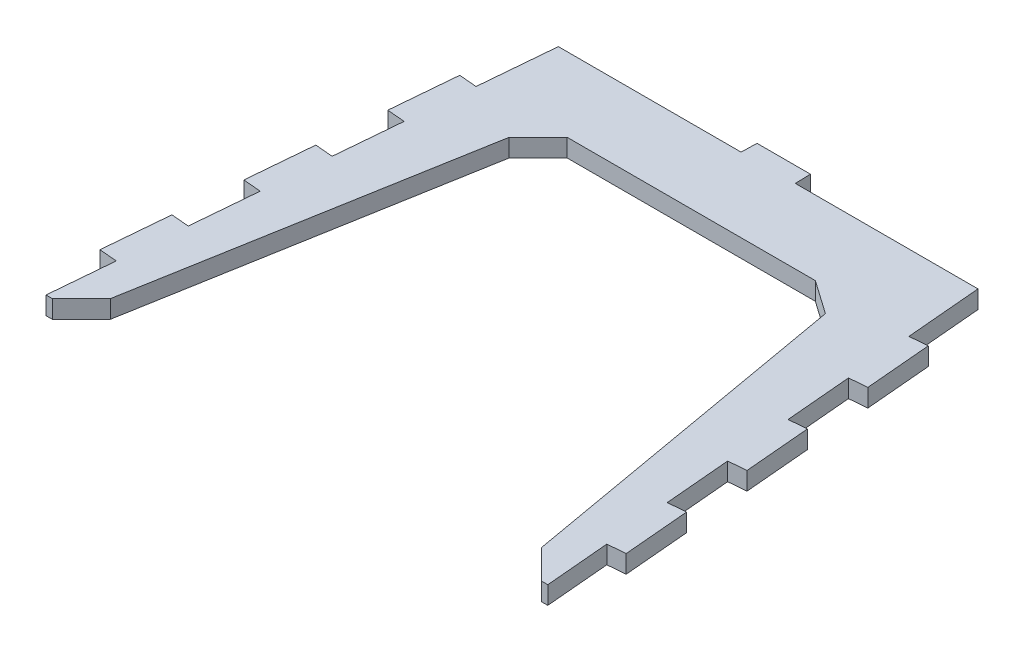
SolidWorks part; units mm, degrees
note: '?' marks a value the reader was unsure of.
ref_plane "Front Plane" through (0, 0, 0) normal (0, 0, 1) x (1, 0, 0)
ref_plane "Top Plane" through (0, 0, 0) normal (0, 1, 0) x (1, 0, 0)
ref_plane "Right Plane" through (0, 0, 0) normal (1, 0, 0) x (0, 0, -1)
ref_axis "Axis1" through (-88.99, 0, 0) along (1, 0, 0)?
ref_axis "Axis2" through (88.99, 0, -993.4582) along (0.0868, 0, 0.9962)?
ref_axis "Axis3" through (-170.7796, 0, -55) along (0.0868, 0, -0.9962)?
ref_point "Point1"
ref_point "Point2"
ref_axis "Axis6" through (-196.0379, 0, 62.0462) along (1, 0, 0)?
sketch "Sketch2" plane through (0, 0, 0) normal (0, 1, 0) x (1, 0, 0)
  line L0 (-190.6304, 0) -> (-225, -394.3588)
  line L1 (190.6304, 0) -> (225, -394.3588)
  line L2 (225, -394.3588) -> (-225, -394.3588) construction
  line L3 (225, -394.3588) -> (220.173, -338.9734) construction
  line L4 (-225, -394.3588) -> (-220.173, -338.9734) construction
  line L5 (-190.6304, 0) -> (190.6304, 0)
  line L6 (-88.99, 0) -> (88.99, 0) construction
  line L7 (0, 0) -> (0, -394.3588) construction
  line L8 (-175.5731, 0) -> (-209.9427, -394.3588) construction
  line L9 (175.5731, 0) -> (209.9427, -394.3588) construction
  line L10 (88.99, 993.4582) -> (170.7796, 55) construction
  line L11 (-170.7796, 55) -> (88.99, 3035.609) construction
  line L12 (-225, -394.3588) -> (-184.6553, -394.3588)
  line L13 (-184.6553, -394.3588) -> (-126.1737, -62.0462)
  line L14 (-126.1737, -62.0462) -> (126.1737, -62.0462)
  line L15 (126.1737, -62.0462) -> (184.6553, -394.3588)
  line L16 (184.6553, -394.3588) -> (225, -394.3588)
  line L18 (-204.9433, -394.3588) -> (-153.1585, 0) construction
  line L19 (-204.9433, -394.3588) -> (-224.7731, -391.7549) construction
  line L20 (-196.0379, -62.0462) -> (196.0379, -62.0462) construction
  dimension "D1" = 5
  dimension "D2" = 20
extrude "Boss-Extrude1" add sketch "Sketch2" against normal up to vertex (15 mm away)
chamfer "Chamfer1" distance 20 angle 45 2 edges at (-184.6553, -7.5, 394.3588) (184.6553, -7.5, 394.3588)
chamfer "Chamfer2" distance 20 angle 45 2 edges at (126.1737, -7.5, 62.0462) (-126.1737, -7.5, 62.0462)
sketch "Sketch3" plane through (0, 0, 0) normal (0, 1, 0) x (1, 0, 0)
  line L0 (196.0379, -62.0462) -> (-196.0379, -62.0462) construction
  line L1 (-126.1737, -62.0462) -> (126.1737, -62.0462) construction
  line L2 (-190.6304, 0) -> (-225, -394.3588) construction
  line L3 (-225, -394.3588) -> (225, -394.3588) construction
  line L4 (225, -394.3588) -> (190.6304, 0) construction
  line L5 (190.6304, 0) -> (-190.6304, 0) construction
  line L6 (-190.6304, 0) -> (190.6304, 0) construction
  line L7 (-190.6304, 0) -> (-225, -394.3588) construction
  line L8 (190.6304, 0) -> (225, -394.3588) construction
  line L9 (225, -394.3588) -> (-225, -394.3588) construction
  line L10 (-175.5731, 0) -> (-209.9427, -394.3588) construction
  line L11 (175.5731, 0) -> (209.9427, -394.3588) construction
  line L12 (175.5731, 0) -> (209.9427, -394.3588) construction
  line L13 (-175.5731, 0) -> (-209.9427, -394.3588) construction
  line L14 (-196.0379, -62.0462) -> (-181.0941, -63.3486)
  line L15 (-181.0941, -63.3486) -> (-175.5731, 0)
  line L16 (-175.5731, 0) -> (-190.6304, 0)
  line L17 (-190.6304, 0) -> (-196.0379, -62.0462)
  line L18 (-210.5189, -228.2025) -> (-195.5752, -229.5049)
  line L19 (-195.5752, -229.5049) -> (-200.4022, -284.8903)
  line L20 (-200.4022, -284.8903) -> (-215.346, -283.5879)
  line L21 (-215.346, -283.5879) -> (-210.5189, -228.2025)
  line L22 (-220.173, -338.9734) -> (-225, -394.3588)
  line L23 (-225, -394.3588) -> (-209.9427, -394.3588)
  line L24 (-209.9427, -394.3588) -> (-205.2292, -340.2758)
  line L25 (-205.2292, -340.2758) -> (-220.173, -338.9734)
  line L26 (-200.8649, -117.4317) -> (-205.6919, -172.8171)
  line L27 (-205.6919, -172.8171) -> (-190.7481, -174.1195)
  line L28 (-190.7481, -174.1195) -> (-185.9211, -118.7341)
  line L29 (-185.9211, -118.7341) -> (-200.8649, -117.4317)
  line L30 (-188.566, -62.6974) -> (-193.393, -118.0829) construction
  line L31 (-198.22, -173.4683) -> (-203.0471, -228.8537) construction
  line L32 (-207.8741, -284.2391) -> (-212.7011, -339.6246) construction
extrude "Cut-Extrude1" cut sketch "Sketch3" against normal through all
mirror "Mirror1" about plane through (0, 0, 0) normal (1, 0, 0) of "Cut-Extrude1"
sketch "Sketch4" plane through (0, 0, 0) normal (0, 1, 0) x (1, 0, 0)
  line L0 (-190.6304, 0) -> (-189.3205, 15.03) construction
  line L1 (-189.3205, 15.03) -> (-112.6095, 15.03) construction
  line L2 (-112.6095, 15.03) -> (-115.2545, 0) construction
  line L3 (-190.6304, 0) -> (-225, -394.3588) construction
  line L7 (-175.6304, 0) -> (-130.2545, 0)
  line L8 (-184.6553, -394.3588) -> (-126.1737, -62.0462) construction
  line L9 (-130.2545, 0) -> (-115.2545, 0) construction
  line L10 (-175.6304, 0) -> (-190.6304, 0) construction
  line L11 (-190.6304, 0) -> (190.6304, 0) construction
  line L12 (-189.3205, 15.03) -> (-188.0181, 29.9734) construction
  line L13 (-175.6304, 0) -> (-175.2891, 13.0336)
  line L14 (-175.2891, 13.0336) -> (-130.5958, 13.0336)
  line L15 (-130.5958, 13.0336) -> (-130.2545, 0)
  line L16 (-152.9425, 13.0336) -> (-152.9425, 0) construction
  line L17 (-189.4944, 13.0336) -> (-175.2891, 13.0336) construction
  dimension "D1" = 3
sketch "Sketch5" plane through (0, 0, 0) normal (0, 1, 0) x (1, 0, 0)
  line L0 (-22.6879, 0) -> (22.6879, 0)
  line L2 (22.6879, 0) -> (22.3466, 13.0336)
  line L3 (22.3466, 13.0336) -> (-22.3466, 13.0336)
  line L4 (-22.3466, 13.0336) -> (-22.6879, 0)
  line L5 (0, 0) -> (0, 13.0336) construction
  line L6 (0, 0) -> (0, -394.3588) construction
  line L7 (-175.2891, 13.0336) -> (-130.5958, 13.0336) construction
  line L8 (-190.6304, 0) -> (190.6304, 0) construction
  line L9 (-175.6304, 0) -> (-130.2545, 0) construction
extrude "Boss-Extrude2" add sketch "Sketch5" against normal up to surface (15 mm away) up to face at (-0.1514, -15, 206.6008)
